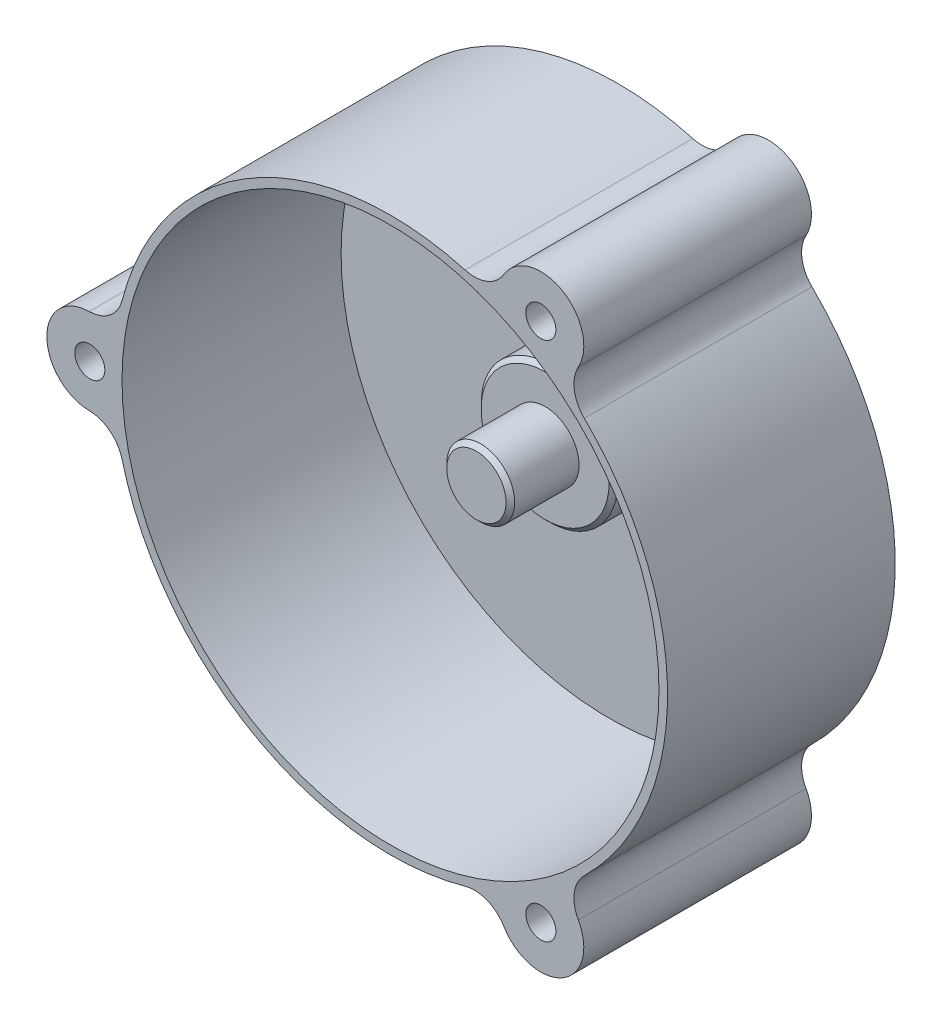
SolidWorks part; units mm, degrees
ref_plane "Front" through (0, 0, 0) normal (0, 0, 1) x (1, 0, 0)
ref_plane "Top" through (0, 0, 0) normal (0, 1, 0) x (1, 0, 0)
ref_plane "Right" through (0, 0, 0) normal (1, 0, 0) x (0, 0, -1)
sketch "Esquisse1" plane through (0, 0, 0) normal (0, 0, 1) x (1, 0, 0)
  circle A0 centre (0, 0) radius 31.25
  dimension "D1" = 62.5
extrude "Boss.-Extru.1" add sketch "Esquisse1" along normal blind 1
sketch "Esquisse2" plane through (0, 0, 1) normal (0, 0, 1) x (1, 0, 0)
  circle A0 centre (0, 0) radius 32.25
  circle A1 centre (0, 0) radius 31.25 construction
  circle A2 centre (0, 0) radius 31.25
  dimension "D1" = 1
extrude "Boss.-Extru.2" add sketch "Esquisse2" along normal blind 25.5 and the other way up to surface (1 mm away) other way up to face at (31.25, 0, 0)
sketch "Esquisse3" plane through (0, 0, 1) normal (0, 0, 1) x (1, 0, 0)
  circle A0 centre (0, 0) radius 7.95
  dimension "D1" = 15.9
extrude "Boss.-Extru.3" add sketch "Esquisse3" along normal blind 7.5
sketch "Esquisse4" plane through (0, 0, 8.5) normal (0, 0, 1) x (1, 0, 0)
  circle A0 centre (0, 0) radius 3.95
  dimension "D1" = 7.9
extrude "Boss.-Extru.4" add sketch "Esquisse4" along normal blind 8
chamfer "Chanfrein1" distance 0.5 angle 45 2 edges at (7.95, 0, 8.5) (3.95, 0, 16.5)
sketch "Esquisse5" plane through (0, 0, 26.5) normal (0, 0, 1) x (1, 0, 0)
  line L0 (-35, 0) -> (0, 0) construction
  arc A0 (-32.0009, -4.0007) -> (-32.0009, 4.0007) centre (-35, 0) cw
  circle A1 centre (0, 0) radius 32.25 construction
  arc A2 (-32.0009, 4.0007) -> (-32.0009, -4.0007) centre (0, 0) ccw
  dimension "D1" = 5
  dimension "D2" = 35
extrude "Boss.-Extru.5" add sketch "Esquisse5" against normal up to surface (26.5 mm away) up to face at (32.25, 0, 0)
sketch "Esquisse6" plane through (0, 0, 26.5) normal (0, 0, 1) x (1, 0, 0)
  circle A0 centre (-35, 0) radius 1.75
  dimension "D1" = 3.5
extrude "Enlèv. mat.-Extru.1" cut sketch "Esquisse6" against normal blind 10
fillet "Congé1" radius 4 2 edges at (-32.0009, 4.0007, 13.25) (-32.0009, -4.0007, 13.25)
pattern_circular "Répétition circulaire2" count 3 over 360 about axis through (0, 0, 26.5) along (0, 0, 1) of "Boss.-Extru.5", "Enlèv. mat.-Extru.1", "Congé1"
sketch "Esquisse7" plane through (0, 0, 26.5) normal (0, 0, 1) x (1, 0, 0)
  arc A12 (-35.064, 4.9996) -> (-35.064, -4.9996) centre (-35, 0) ccw
  arc A13 (-31.2404, -8.0062) -> (-35.064, -4.9996) centre (-35.1152, -8.9993) ccw
  arc A14 (-31.2404, -8.0062) -> (8.6866, -31.0581) centre (0, 0) ccw
  arc A15 (13.2022, -32.8661) -> (8.6866, -31.0581) centre (9.764, -34.9103) ccw
  arc A16 (13.2022, -32.8661) -> (21.8618, -27.8665) centre (17.5, -30.3109) ccw
  arc A17 (22.5538, -23.0519) -> (21.8618, -27.8665) centre (25.3512, -25.911) ccw
  arc A18 (22.5538, -23.0519) -> (22.5538, 23.0519) centre (0, 0) ccw
  arc A19 (21.8618, 27.8665) -> (22.5538, 23.0519) centre (25.3512, 25.911) ccw
  arc A20 (21.8618, 27.8665) -> (13.2022, 32.8661) centre (17.5, 30.3109) ccw
  arc A21 (8.6866, 31.0581) -> (13.2022, 32.8661) centre (9.764, 34.9103) ccw
  arc A22 (8.6866, 31.0581) -> (-31.2404, 8.0062) centre (0, 0) ccw
  arc A23 (-35.064, 4.9996) -> (-31.2404, 8.0062) centre (-35.1152, 8.9993) ccw
  arc A24 (-35.064, 4.9996) -> (-35.064, -4.9996) centre (-35, 0) ccw
  arc A25 (-31.2404, -8.0062) -> (-35.064, -4.9996) centre (-35.1152, -8.9993) ccw
  arc A26 (-31.2404, -8.0062) -> (8.6866, -31.0581) centre (0, 0) ccw
  arc A27 (13.2022, -32.8661) -> (8.6866, -31.0581) centre (9.764, -34.9103) ccw
  arc A28 (13.2022, -32.8661) -> (21.8618, -27.8665) centre (17.5, -30.3109) ccw
  arc A29 (22.5538, -23.0519) -> (21.8618, -27.8665) centre (25.3512, -25.911) ccw
  arc A30 (22.5538, -23.0519) -> (22.5538, 23.0519) centre (0, 0) ccw
  arc A31 (21.8618, 27.8665) -> (22.5538, 23.0519) centre (25.3512, 25.911) ccw
  arc A32 (21.8618, 27.8665) -> (13.2022, 32.8661) centre (17.5, 30.3109) ccw
  arc A33 (8.6866, 31.0581) -> (13.2022, 32.8661) centre (9.764, 34.9103) ccw
  arc A34 (8.6866, 31.0581) -> (-31.2404, 8.0062) centre (0, 0) ccw
  arc A35 (-35.064, 4.9996) -> (-31.2404, 8.0062) centre (-35.1152, 8.9993) ccw
  dimension "D1" = 0
extrude "Enlèv. mat.-Extru.2" [suppressed] cut sketch "Esquisse7" against normal blind 25.5
sketch "Esquisse8" plane through (0, 0, 1) normal (0, 0, 1) x (1, 0, 0)
  circle A0 centre (0, 0) radius 3.95
  dimension "D1" = 7.9
extrude "Boss.-Extru.6" [suppressed] add sketch "Esquisse8" along normal blind 8
sketch "Esquisse9" plane through (0, 0, 1) normal (0, 0, 1) x (1, 0, 0)
  circle A0 centre (-35, 0) radius 2.25
  circle A1 centre (17.5, 30.3109) radius 2.25
  circle A2 centre (17.5, -30.3109) radius 2.25
  dimension "D1" = 4.5
extrude "Enlèv. mat.-Extru.3" [suppressed] cut sketch "Esquisse9" against normal through all
chamfer "Chanfrein2" [suppressed] distance 1 angle 45
sketch "Esquisse10" plane through (0, 0, 1) normal (0, 0, 1) x (1, 0, 0)
  circle A0 centre (0, 0) radius 31
  circle A1 centre (0, 0) radius 27.25
  dimension "D1" = 62
  dimension "D2" = 54.5
extrude "Boss.-Extru.7" [suppressed] add sketch "Esquisse10" along normal blind 0.5
sketch "Esquisse11" [suppressed] plane through (0, 0, 1) normal (0, 0, 1) x (1, 0, 0)
  circle A12 centre (0, 0) radius 31 construction
  circle A13 centre (0, 0) radius 31
  arc A24 (-35.064, 4.9996) -> (-31.2404, 8.0062) centre (-35.1152, 8.9993) ccw
  arc A25 (-35.064, 4.9996) -> (-35.064, -4.9996) centre (-35, 0) ccw
  arc A26 (-31.2404, -8.0062) -> (-35.064, -4.9996) centre (-35.1152, -8.9993) ccw
  arc A27 (-31.2404, -8.0062) -> (8.6866, -31.0581) centre (0, 0) ccw
  arc A28 (13.2022, -32.8661) -> (8.6866, -31.0581) centre (9.764, -34.9103) ccw
  arc A29 (13.2022, -32.8661) -> (21.8618, -27.8665) centre (17.5, -30.3109) ccw
  arc A30 (22.5538, -23.0519) -> (21.8618, -27.8665) centre (25.3512, -25.911) ccw
  arc A31 (22.5538, -23.0519) -> (22.5538, 23.0519) centre (0, 0) ccw
  arc A32 (21.8618, 27.8665) -> (22.5538, 23.0519) centre (25.3512, 25.911) ccw
  arc A33 (21.8618, 27.8665) -> (13.2022, 32.8661) centre (17.5, 30.3109) ccw
  arc A34 (8.6866, 31.0581) -> (13.2022, 32.8661) centre (9.764, 34.9103) ccw
  arc A35 (8.6866, 31.0581) -> (-31.2404, 8.0062) centre (0, 0) ccw
  arc A36 (-35.064, 4.9996) -> (-31.2404, 8.0062) centre (-35.1152, 8.9993) ccw
  arc A37 (-35.064, 4.9996) -> (-35.064, -4.9996) centre (-35, 0) ccw
  arc A38 (-31.2404, -8.0062) -> (-35.064, -4.9996) centre (-35.1152, -8.9993) ccw
  arc A39 (-31.2404, -8.0062) -> (8.6866, -31.0581) centre (0, 0) ccw
  arc A40 (13.2022, -32.8661) -> (8.6866, -31.0581) centre (9.764, -34.9103) ccw
  arc A41 (13.2022, -32.8661) -> (21.8618, -27.8665) centre (17.5, -30.3109) ccw
  arc A42 (22.5538, -23.0519) -> (21.8618, -27.8665) centre (25.3512, -25.911) ccw
  arc A43 (22.5538, -23.0519) -> (22.5538, 23.0519) centre (0, 0) ccw
  arc A44 (21.8618, 27.8665) -> (22.5538, 23.0519) centre (25.3512, 25.911) ccw
  arc A45 (21.8618, 27.8665) -> (13.2022, 32.8661) centre (17.5, 30.3109) ccw
  arc A46 (8.6866, 31.0581) -> (13.2022, 32.8661) centre (9.764, 34.9103) ccw
  arc A47 (8.6866, 31.0581) -> (-31.2404, 8.0062) centre (0, 0) ccw
  dimension "D1" = 0
extrude "Enlèv. mat.-Extru.4" [suppressed] cut sketch "Esquisse11" against normal blind 0.5
sketch "Esquisse12" [suppressed] plane through (0, 0, 0) normal (0, 0, -1) x (-1, 0, 0)
  circle A0 centre (35, 0) radius 2.25 construction
  circle A1 centre (-17.5, -30.3109) radius 2.25 construction
  circle A2 centre (-17.5, 30.3109) radius 2.25 construction
  circle A3 centre (35, 0) radius 2.25
  circle A4 centre (-17.5, -30.3109) radius 2.25
  circle A5 centre (-17.5, 30.3109) radius 2.25
  arc A12 (35.064, -4.9996) -> (35.064, 4.9996) centre (35, 0) ccw
  arc A13 (31.2404, 8.0062) -> (35.064, 4.9996) centre (35.1152, 8.9993) ccw
  arc A14 (31.2404, 8.0062) -> (-8.6866, 31.0581) centre (0, 0) ccw
  arc A15 (-13.2022, 32.8661) -> (-8.6866, 31.0581) centre (-9.764, 34.9103) ccw
  arc A16 (-13.2022, 32.8661) -> (-21.8618, 27.8665) centre (-17.5, 30.3109) ccw
  arc A17 (-22.5538, 23.0519) -> (-21.8618, 27.8665) centre (-25.3512, 25.911) ccw
  arc A18 (-22.5538, 23.0519) -> (-22.5538, -23.0519) centre (0, 0) ccw
  arc A19 (-21.8618, -27.8665) -> (-22.5538, -23.0519) centre (-25.3512, -25.911) ccw
  arc A20 (-21.8618, -27.8665) -> (-13.2022, -32.8661) centre (-17.5, -30.3109) ccw
  arc A21 (-8.6866, -31.0581) -> (-13.2022, -32.8661) centre (-9.764, -34.9103) ccw
  arc A22 (-8.6866, -31.0581) -> (31.2404, -8.0062) centre (0, 0) ccw
  arc A23 (35.064, -4.9996) -> (31.2404, -8.0062) centre (35.1152, -8.9993) ccw
  arc A24 (35.064, -4.9996) -> (35.064, 4.9996) centre (35, 0) ccw
  arc A25 (31.2404, 8.0062) -> (35.064, 4.9996) centre (35.1152, 8.9993) ccw
  arc A26 (31.2404, 8.0062) -> (-8.6866, 31.0581) centre (0, 0) ccw
  arc A27 (-13.2022, 32.8661) -> (-8.6866, 31.0581) centre (-9.764, 34.9103) ccw
  arc A28 (-13.2022, 32.8661) -> (-21.8618, 27.8665) centre (-17.5, 30.3109) ccw
  arc A29 (-22.5538, 23.0519) -> (-21.8618, 27.8665) centre (-25.3512, 25.911) ccw
  arc A30 (-22.5538, 23.0519) -> (-22.5538, -23.0519) centre (0, 0) ccw
  arc A31 (-21.8618, -27.8665) -> (-22.5538, -23.0519) centre (-25.3512, -25.911) ccw
  arc A32 (-21.8618, -27.8665) -> (-13.2022, -32.8661) centre (-17.5, -30.3109) ccw
  arc A33 (-8.6866, -31.0581) -> (-13.2022, -32.8661) centre (-9.764, -34.9103) ccw
  arc A34 (-8.6866, -31.0581) -> (31.2404, -8.0062) centre (0, 0) ccw
  arc A35 (35.064, -4.9996) -> (31.2404, -8.0062) centre (35.1152, -8.9993) ccw
  point P0 (0, 0)
  dimension "D1" = 0
extrude "Boss.-Extru.8" [suppressed] add sketch "Esquisse12" along normal blind 1
sketch "Esquisse13" [suppressed] plane through (0, 0, 1.5) normal (0, 0, 1) x (1, 0, 0)
  line L0 (-14.5625, 25.223) -> (-13.625, 23.5992) construction
  line L1 (-14.5625, 25.223) -> (-15.5, 26.8468) construction
  line L2 (-35, 0) -> (-14.5625, 25.223) construction
  line L3 (-14.5625, 25.223) -> (17.5, 30.3109) construction
  line L4 (-13.625, 23.5992) -> (0, 0) construction
  line L5 (29.125, 0) -> (27.25, 0) construction
  line L6 (29.125, 0) -> (31, 0) construction
  line L7 (-14.5625, -25.223) -> (-13.625, -23.5992) construction
  line L8 (-14.5625, -25.223) -> (-15.5, -26.8468) construction
  circle A0 centre (-14.5625, 25.223) radius 1.25
  circle A1 centre (0, 0) radius 27.25 construction
  circle A2 centre (0, 0) radius 31 construction
  circle A3 centre (29.125, 0) radius 1.25
  circle A4 centre (-14.5625, -25.223) radius 1.25
  point P24 (0, 0)
  dimension "D1" = 2.5
  dimension "D2" = 3
extrude "Enlèv. mat.-Extru.5" [suppressed] cut sketch "Esquisse13" against normal through all
sketch "Esquisse14" [suppressed] plane through (0, 0, 26.5) normal (0, 0, 1) x (1, 0, 0)
  circle A0 centre (0, 0) radius 7.95
  circle A1 centre (0, 0) radius 50
  dimension "D1" = 100
  dimension "D2" = 15.9
extrude "Enlèv. mat.-Extru.6" [suppressed] cut sketch "Esquisse14" against normal through all both and the other way through all
sketch "Esquisse15" [suppressed] plane through (0, 0, 0) normal (0, 0, -1) x (-1, 0, 0)
  line L0 (0, 0) -> (5.7, 0) construction
  circle A0 centre (5.7, 0) radius 1.3
  circle A1 centre (-2.85, -4.9363) radius 1.3
  circle A2 centre (-2.85, 4.9363) radius 1.3
  point P10 (0, 0)
  dimension "D1" = 2.6
  dimension "D2" = 5.7
  dimension "D3" = 3
extrude "Enlèv. mat.-Extru.7" [suppressed] cut sketch "Esquisse15" against normal through all
